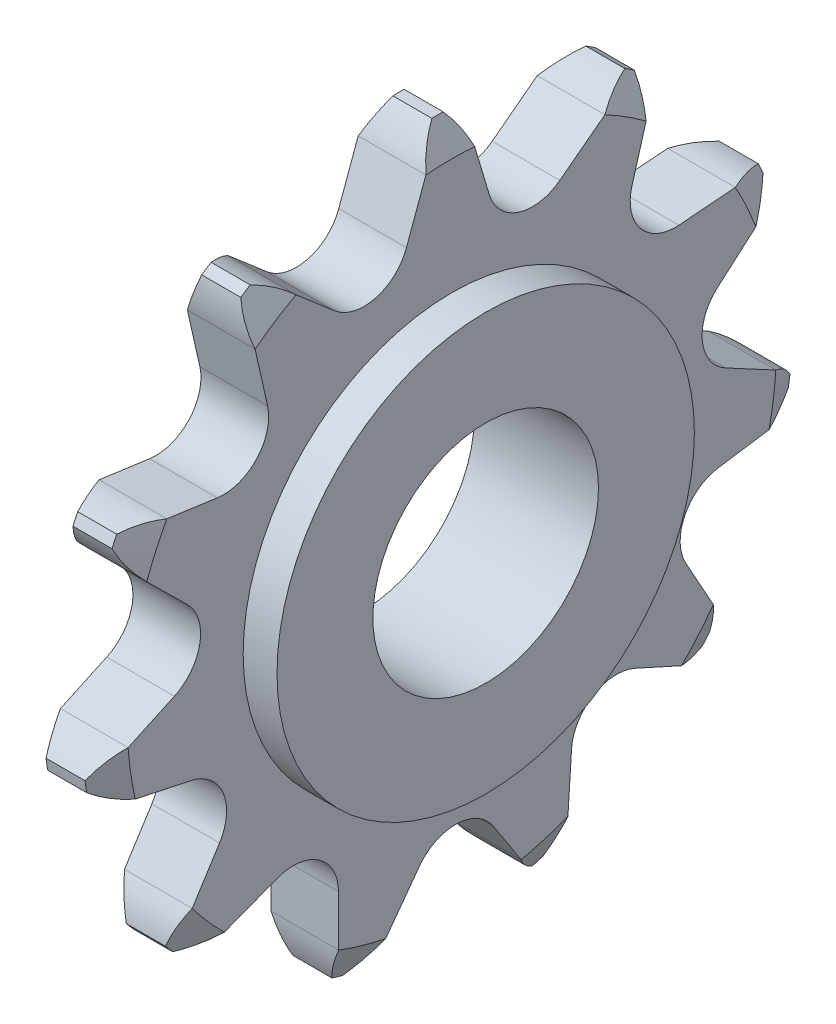
SolidWorks part; units mm, degrees
ref_plane "Front Plane" through (0, 0, 0) normal (0, 0, 1) x (1, 0, 0)
ref_plane "Top Plane" through (0, 0, 0) normal (0, 1, 0) x (1, 0, 0)
ref_plane "Right Plane" through (0, 0, 0) normal (1, 0, 0) x (0, 0, -1)
sketch "Sketch1" plane through (0, 0, 0) normal (1, 0, 0) x (0, 0, -1)
  circle A0 centre (0, 0) radius 18.5
  circle A1 centre (0, 0) radius 10
  dimension "D1" = 37
  dimension "D2" = 20
extrude "Boss-Extrude1" add sketch "Sketch1" along normal blind 11
ref_plane "Plane1" through (8, 0, 0) normal (1, 0, 0) x (0, 0, -1)
sketch "Sketch2" plane through (8, 0, 0) normal (1, 0, 0) x (0, 0, -1)
  circle A0 centre (0, 0) radius 10
  circle A1 centre (0, 0) radius 31.5
  dimension "D1" = 63
extrude "Boss-Extrude2" add sketch "Sketch2" against normal blind 6
chamfer "Chamfer1" distance 1.27 angle 65 2 edges at (2, 0, -31.5) (8, 0, -31.5) first distance on face at (2, 0, -31.5)
sketch "Sketch3" plane through (11, 0, 0) normal (1, 0, 0) x (0, 0, -1)
  line L0 (0, 34.6833) -> (0, 0) construction
  line L1 (0, 0) -> (21.617, 33.6368) construction
  line L2 (2.025, 28.7051) -> (3.3168, 24.3739)
  line L3 (9.5719, 22.3338) -> (13.5704, 25.3758)
  line L4 (0, 31.5) -> (0, 32.6109)
  line L5 (0, 32.6109) -> (18.7531, 29.4926)
  line L6 (18.7531, 29.4926) -> (17.0302, 26.4995)
  arc A0 (0, 31.5) -> (0.5, 31.496) centre (0, 0) cw
  arc A1 (17.0302, 26.4995) -> (16.6074, 26.7665) centre (0, 0) ccw
  arc A2 (9.5719, 22.3338) -> (3.3168, 24.3739) centre (7.15, 25.5172) cw
  circle A3 centre (0, 0) radius 22.5 construction
  circle A4 centre (0, 0) radius 31.5 construction
  arc A5 (0.5, 31.496) -> (2.025, 28.7051) centre (-5.2771, 26.5272) cw
  arc A6 (16.6074, 26.7665) -> (13.5704, 25.3758) centre (18.1842, 19.3114) ccw
  circle A7 centre (0, 0) radius 28.7765 construction
  dimension "D2" = 45
  dimension "D4" = 0.5
  dimension "D5" = 7.62
  dimension "D6" = 7.62
  dimension "D7" = 4
  dimension "D1" = 32.727
  dimension "D3" = 0.5
extrude "Cut-Extrude1" cut sketch "Sketch3" against normal through all
ref_axis "Axis1" through (11, 0, 0) along (-1, 0, 0)
pattern_circular "CirPattern1" count 11 over 360 about axis through (11, 0, 0) along (-1, 0, 0) of "Cut-Extrude1"
